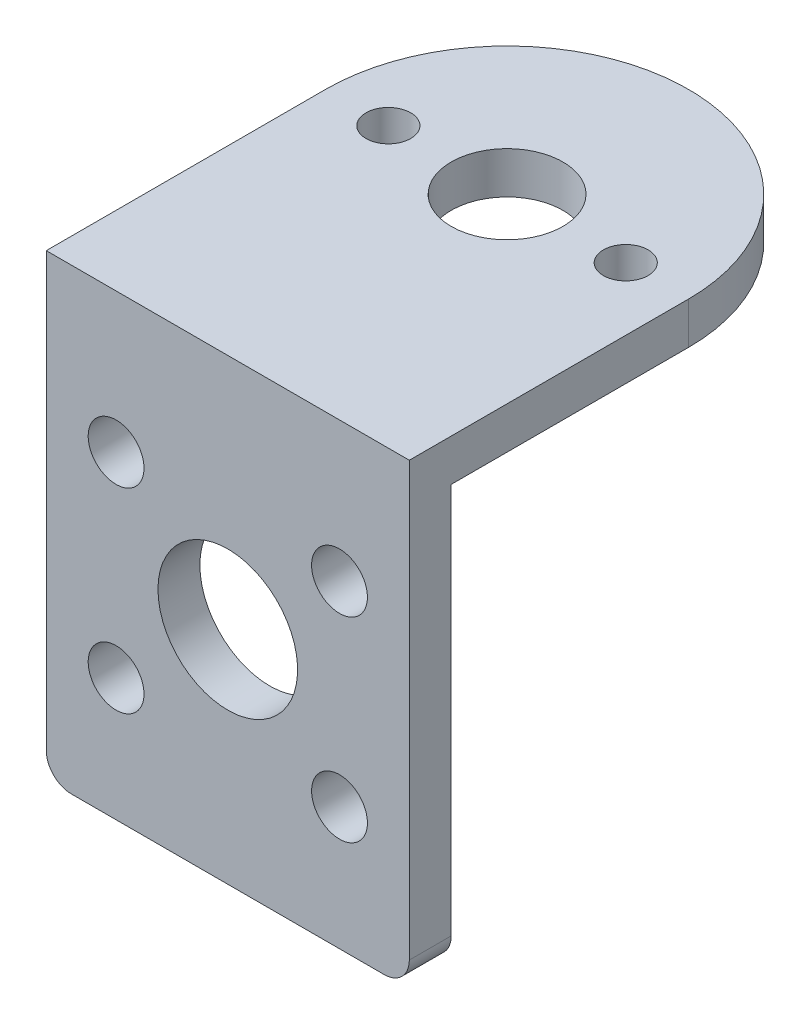
SolidWorks part; units mm, degrees
ref_plane "前视基准面" through (0, 0, 0) normal (0, 0, 1) x (1, 0, 0)
ref_plane "上视基准面" through (0, 0, 0) normal (0, 1, 0) x (1, 0, 0)
ref_plane "右视基准面" through (0, 0, 0) normal (1, 0, 0) x (0, 0, -1)
sketch "草图1" plane through (0, 0, 0) normal (0, 1, 0) x (1, 0, 0)
  line L0 (-33.0672, 0) -> (35.0413, 0) construction
  line L1 (0, -19.8033) -> (0, 24.7387) construction
  line L2 (-13, 0) -> (-13, -20)
  line L3 (13, 0) -> (13, -20)
  line L4 (13, -20) -> (-13, -20)
  line L5 (-13, -17) -> (13, -17)
  circle A0 centre (0, 0) radius 4
  circle A1 centre (-8.5, 0) radius 1.6
  circle A2 centre (8.5, 0) radius 1.6
  circle A3 centre (0, 0) radius 13
  dimension "D1" = 8
  dimension "D2" = 3.2
  dimension "D4" = 26
  dimension "D3" = 17
  dimension "D5" = 20
  dimension "D6" = 3
extrude "凸台-拉伸1" add sketch "草图1" along normal blind 3 contours A3 A0 A1 A2 | A3 L2 L5 L3 | L5 L2 L4 L3 region at (0, 0, 13.3106) region at (0, 0, -12.6323) region at (0, 0, 18.5)
sketch "草图2" plane through (0, 0, 0) normal (0, -1, 0) x (1, 0, 0)
  line L0 (-13, 0) -> (-13, 20) construction
  line L1 (13, 20) -> (-13, 20)
  line L2 (13, 20) -> (13, 17)
  line L3 (13, 17) -> (-13, 17)
  line L4 (-13, 20) -> (-13, 17)
  dimension "D1" = 3
extrude "凸台-拉伸2" add sketch "草图2" along normal blind 28 contours L2 L1 L4 L3
sketch "草图3" plane through (0, 0, 17) normal (0, 0, -1) x (-1, 0, 0)
  line L0 (13, -14) -> (-13, -14) construction
  line L1 (13, -28) -> (13, 0) construction
  line L2 (-13, -28) -> (-13, 0) construction
  line L3 (0, -28) -> (0, 0) construction
  line L4 (-13, -28) -> (13, -28) construction
  line L5 (-13, -18.0795) -> (-13, -28)
  line L6 (-13, -28) -> (13, -28)
  line L7 (13, -28) -> (13, -19.1297)
  line L8 (-11.2, -29.8) -> (11.2, -29.8)
  circle A0 centre (0, -14) radius 5
  circle A1 centre (8, -7) radius 2
  circle A2 centre (8, -21) radius 2
  circle A3 centre (-8, -21) radius 2
  circle A4 centre (-8, -7) radius 2
  arc A5 (-13, -28) -> (-11.2, -29.8) centre (-11.2, -28) ccw
  arc A6 (13, -28) -> (11.2, -29.8) centre (11.2, -28) cw
  line M3 (-13, -28) -> (13, -28)
  dimension "D1" = 4
  dimension "D4" = 10
  dimension "D2" = 16
  dimension "D3" = 14
  dimension "D5" = 1.8
extrude "切除-拉伸1" cut sketch "草图3" against normal through all contours A4 | A0 | A1 | A2 | A3
extrude "凸台-拉伸3" add sketch "草图3<4>" against normal blind 3 contours A6 A5 L8 M3 region at (0, -28.8848, 17)
sketch "草图3<4>" plane through (0, 0, 17) normal (0, 0, -1) x (-1, 0, 0) same geometry as "草图3"
